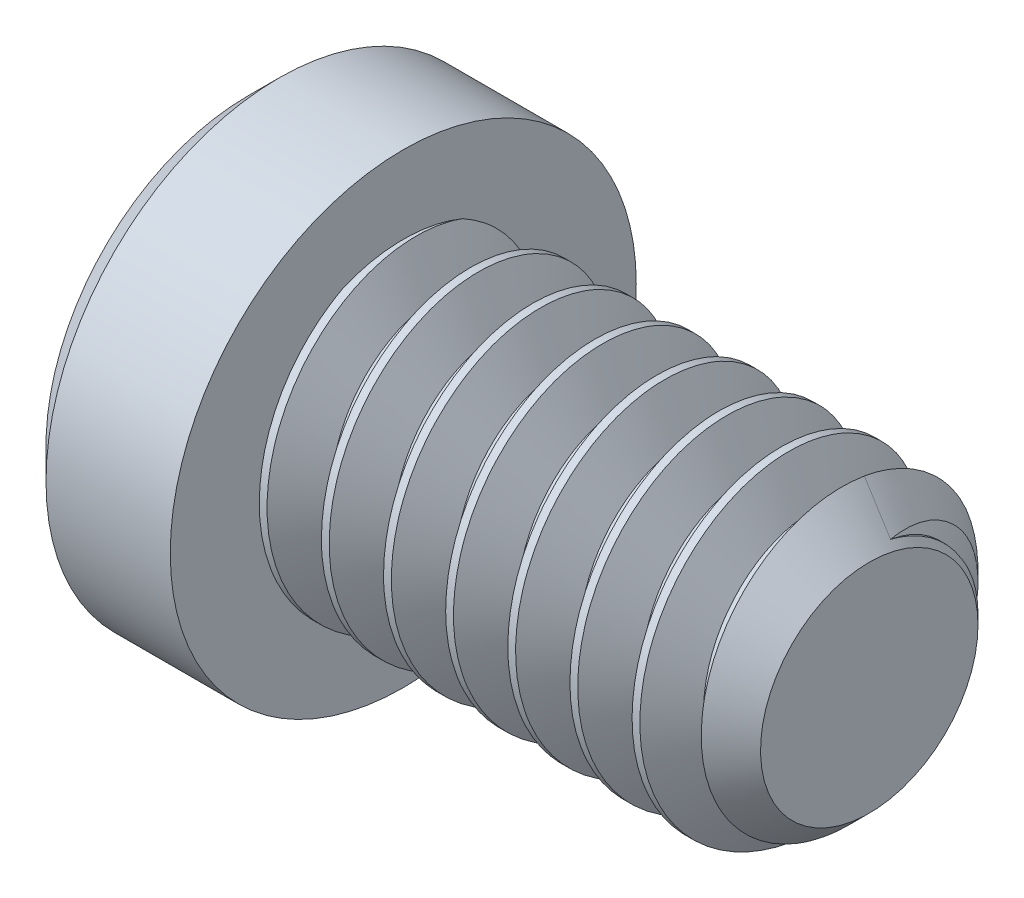
SolidWorks part; units mm, degrees
ref_plane "Front Plane" through (0, 0, 0) normal (0, 0, 1) x (1, 0, 0)
ref_plane "Top Plane" through (0, 0, 0) normal (0, 1, 0) x (1, 0, 0)
ref_plane "Right Plane" through (0, 0, 0) normal (1, 0, 0) x (0, 0, -1)
sketch "Sketch1" plane through (0, 0, 0) normal (0, 0, 1) x (1, 0, 0)
  line L0 (4.7625, 0) -> (-4.7625, 0) construction
  line L1 (4.7625, 3.175) -> (4.7625, -3.175) construction
  line L2 (-4.7625, 4.7625) -> (-4.7625, -4.7625) construction
  line L3 (-4.7625, 4.7625) -> (-7.3025, 4.7625) construction
  line L4 (-7.3025, 4.7625) -> (-7.9375, 4.1275) construction
  line L5 (-7.9375, 4.1275) -> (-7.9375, -4.1275) construction
  line L6 (-7.9375, -4.1275) -> (-7.3025, -4.7625) construction
  line L7 (-7.3025, -4.7625) -> (-4.7625, -4.7625) construction
  point P7 (-5.5499, 0)
  point P12 (-0.3175, -3.175)
  dimension "D1" = 45
  dimension "D2" = 5.08
  dimension "Dec." = 6.35
  dimension "Length" = 9.525
  dimension "Head Dia" = 9.525
  dimension "Head Height" = 3.175
  dimension "Hex Depth" = 2.3876
  dimension "Chamfer" = 0.635
ref_plane "Plane1" through (4.7625, 0, 0) normal (1, 0, 0) x (0, 0, -1)
ref_plane "Plane2" through (-7.9375, 0, 0) normal (1, 0, 0) x (0, 0, -1)
sketch "Sketch2" plane through (4.7625, 0, 0) normal (1, 0, 0) x (0, 0, -1)
  circle A0 centre (0, 0) radius 3.175
extrude "Boss-Extrude1" add sketch "Sketch2" against normal up to vertex (9.525 mm away) up to point (-4.7625, 0, 0)
sketch "Sketch3" plane through (4.7625, 0, 0) normal (1, 0, 0) x (0, 0, -1)
  circle A0 centre (0, 0) radius 3.175 construction
  circle A1 centre (0, 0) radius 3.175
curve "Helix/Spiral1" pitch 1.27 height 10.795 radius 3.175 centre (4.7625, 0, 0) axis (-1, 0, 0) start towards (0, 1, 0) parameters "Pitch"=1.27
chamfer "Chamfer1" distance 0.9525 angle 45 1 edges at (4.7625, 0, -3.175)
sketch "Sketch5" plane through (0, 0, 0) normal (0, 0, 1) x (1, 0, 0)
  line L0 (4.2069, 3.175) -> (5.3181, 3.175)
  line L1 (5.3181, 3.175) -> (4.8419, 2.3501)
  line L2 (4.8419, 2.3501) -> (4.6831, 2.3501)
  line L3 (4.6831, 2.3501) -> (4.2069, 3.175)
  line L4 (4.7625, 2.3501) -> (4.7625, 3.175) construction
  line L5 (4.445, 2.7626) -> (5.08, 2.7626) construction
  dimension "D1" = 60
  dimension "D2" = 0.635
  dimension "D3" = 0.1588
sweep "Cut-Sweep1" cut profiles "Sketch5" path "Helix/Spiral1"
sketch "Sketch4" plane through (-7.9375, 0, 0) normal (1, 0, 0) x (0, 0, -1)
  line L0 (-4.7625, 0.7937) -> (4.7625, 0.7937) construction
  line L1 (0, 1.8331) -> (-1.5875, 0.9165)
  line L2 (-1.5875, 0.9165) -> (-1.5875, -0.9165)
  line L3 (-1.5875, -0.9165) -> (0, -1.8331)
  line L4 (0, -1.8331) -> (1.5875, -0.9165)
  line L5 (1.5875, -0.9165) -> (1.5875, 0.9165)
  line L6 (1.5875, 0.9165) -> (0, 1.8331)
  line L7 (0, 0) -> (0, 0.7937) construction
  circle A0 centre (0, 0) radius 1.5875 construction
  dimension "D1" = 9.525
  dimension "Hex Size" = 3.175
  dimension "D2" = 0.7937
sketch "Sketch6" plane through (0, 0, 0) normal (0, 0, 1) x (1, 0, 0)
  line L0 (-7.3025, 4.7625) -> (-7.9375, 4.1275) construction
  line L1 (-4.7625, 4.7625) -> (-7.3025, 4.7625) construction
  line L2 (-4.7625, 4.7625) -> (-4.7625, -4.7625) construction
  line L3 (-7.9375, 4.1275) -> (-7.9375, -4.1275) construction
  line L4 (-7.3025, 4.7625) -> (-7.9375, 4.1275)
  line L5 (-4.7625, 4.7625) -> (-7.3025, 4.7625)
  line L6 (-4.7625, 4.7625) -> (-4.7625, 0)
  line L7 (-7.9375, 4.1275) -> (-7.9375, 0)
  line L8 (-4.7625, 0) -> (-7.9375, 0) construction
  line L9 (-4.7625, 0) -> (-7.9375, 0)
revolve "Revolve1" add sketch "Sketch6" angle 360 about L8
extrude "Cut-Extrude1" cut sketch "Sketch4" along normal up to vertex (2.3876 mm away) up to point (-5.5499, 0, 0)
sketch "Sketch8" plane through (-7.9375, 0, 0) normal (-1, 0, 0) x (0, 0, 1)
  circle A1 centre (0, 0) radius 1.8331
extrude "Cut-Extrude2" cut sketch "Sketch8" against normal through all draft 45
equation "\"D3@Helix/Spiral1\" = \"Length@Sketch1\"+\"Pitch@Helix/Spiral1\""
equation "\"D3@Sketch5\" = \"Pitch@Helix/Spiral1\"*.125"
equation "\"D2@Sketch5\" = \"Pitch@Helix/Spiral1\"*.50"
equation "\"D1@Chamfer1\" = \"Pitch@Helix/Spiral1\"*.75"
equation "\"D2@Sketch1\" = \"Pitch@Helix/Spiral1\"*4"
equation "\"D1@Sketch4\" = \"Head Dia@Sketch1\""
